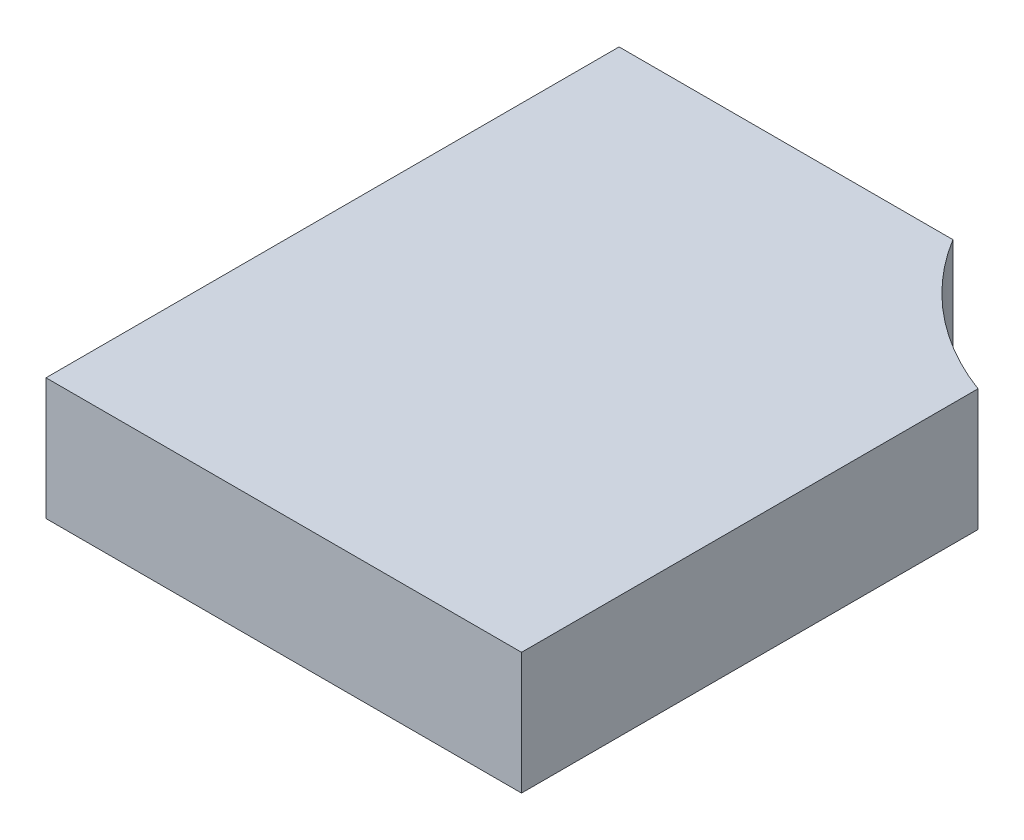
SolidWorks part; units mm, degrees
ref_plane "正面" through (0, 0, 0) normal (0, 0, 1) x (1, 0, 0)
ref_plane "平面" through (0, 0, 0) normal (0, 1, 0) x (1, 0, 0)
ref_plane "右側面" through (0, 0, 0) normal (1, 0, 0) x (0, 0, -1)
sketch "ｽｹｯﾁ1" plane through (0, 0, 0) normal (0, 1, 0) x (1, 0, 0)
  line L1 (0, 0) -> (39, 0)
  line L2 (0, 0) -> (0, -47)
  line L3 (0, -47) -> (39, -47)
  line L4 (39, 0) -> (39, -47)
  circle A0 centre (47, 12) radius 23
  point P7 (0, 0)
  point P9 (11.8195, 0)
  dimension "D5" = 46
  dimension "D1" = 47
  dimension "D2" = 39
  dimension "D3" = 47
  dimension "D4" = 12
extrude "ﾎﾞｽ - 押し出し1" add sketch "ｽｹｯﾁ1" against normal blind 10 contours A0 L1 L2 L3 L4 region at (18.9111, 0, 24.2723)
ref_plane "平面1" through (19.5, 0, 0) normal (1, 0, 0) x (0, 0, -1)
